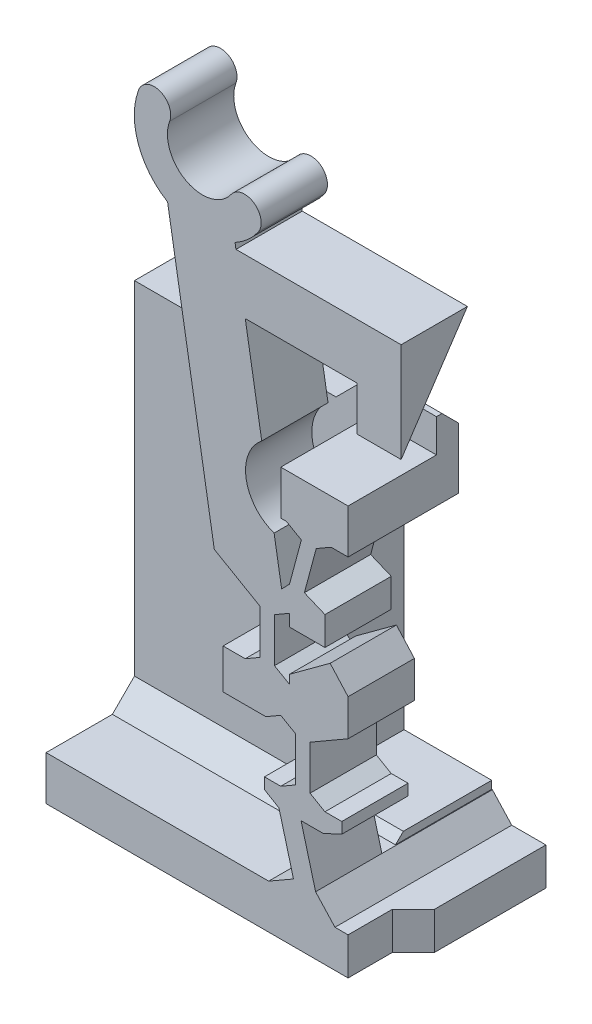
SolidWorks part; units mm, degrees
material "Nylon 6/12"
ref_plane "Front Plane" through (0, 0, 0) normal (0, 0, 1) x (1, 0, 0)
ref_plane "Top Plane" through (0, 0, 0) normal (0, 1, 0) x (1, 0, 0)
ref_plane "Right Plane" through (0, 0, 0) normal (1, 0, 0) x (0, 0, -1)
sketch "Sketch-SkeletonConfigUp" plane through (0, 0, 0) normal (0, 0, 1) x (1, 0, 0)
  line L0 (0, 0) -> (0, -50000) construction
  line L1 (0, 0) -> (4.5811, 6.2164) construction
  line L2 (9.8143, 13.3177) -> (4.5811, 13.945) construction
  line L3 (4.5811, 13.945) -> (2.9713, 10.4094) construction
  line L4 (2.9713, 10.4094) -> (4.5811, 6.2164) construction
  line L5 (4.5811, 13.945) -> (6.2429, 19.1409) construction
  line L6 (2.9713, 10.4094) -> (0.0405, 27.8193) construction
  line L7 (4.5811, 6.2164) -> (9.8143, 13.3177) construction
  line L8 (-587.3593, -797.0242) -> (9.8143, 13.3177) construction
  dimension "D2" = 7.7221
  dimension "D3" = 8.8212
  dimension "D4" = 5.2707
  dimension "D5" = 119.553
  dimension "D6" = 3.8848
  dimension "D7" = 5.4552
  dimension "D8" = 17.6549
  dimension "D9" = 4.4914
  dimension "D10" = 6.745
  dimension "D11" = 145.964
  dimension "D12" = 143.612
sketch "Sketch-SkeletonConfigDown" plane through (0, 0, 0) normal (0, 0, 1) x (1, 0, 0)
  line L0 (0, 0) -> (0, -50000) construction
  line L1 (0, 0) -> (4.5811, 6.2164) construction
  line L2 (9.8143, 13.3177) -> (4.5811, 13.945) construction
  line L3 (4.5811, 13.945) -> (6.1909, 10.4094) construction
  line L4 (6.1909, 10.4094) -> (4.5811, 6.2164) construction
  line L5 (4.5811, 13.945) -> (1.753, 18.6098) construction
  line L6 (6.1909, 10.4094) -> (-8.8652, 19.6294) construction
  line L7 (4.5811, 6.2164) -> (9.8143, 13.3177) construction
  line L8 (-589.9357, -800.5203) -> (9.8143, 13.3177) construction
  dimension "D2" = 7.7221
  dimension "D3" = 8.8212
  dimension "D4" = 5.2707
  dimension "D5" = 119.553
  dimension "D6" = 3.8848
  dimension "D7" = 5.4552
  dimension "D8" = 17.6549
  dimension "D9" = 4.4914
  dimension "D10" = 6.745
  dimension "D11" = 145.964
  dimension "D1" = 143.612
ref_plane "Plane-Cam Base" through (9.128, 0, 0) normal (1, 0, 0) x (0, 0, -1)
ref_plane "Plane-Down-to-Up Derailleur Clearance" through (6.628, 0, 0) normal (1, 0, 0) x (0, 0, -1)
ref_plane "Plane-Cam Cavity Roof" through (5.128, 0, 0) normal (1, 0, 0) x (0, 0, -1)
sketch "Sketch-SwitchBossUp" plane through (0, 0, 0) normal (0, 0, 1) x (1, 0, 0)
  line L0 (3.5811, 11.4759) -> (3.5811, 12.945) construction
  line L5 (5.5811, 12.5552) -> (5.5811, 11.263)
  line L7 (1.5115, 25.1048) -> (1.5536, 24.8548)
  line L8 (-0.4607, 24.7728) -> (1.6966, 11.9577) construction
  line L9 (2.9713, 10.4094) -> (0.0405, 27.8193) construction
  line L11 (0.1364, 21.2256) -> (2.1086, 21.5576) construction
  line L15 (6.628, -23.7286) -> (6.628, 23.7286) construction
  line L16 (2.9713, 10.4094) -> (4.5811, 6.2164) construction
  line L17 (3.5811, 12.945) -> (3.5811, 14.945) construction
  line L18 (5.5811, 12.945) -> (5.5811, 14.945) construction
  line L19 (4.2561, 13.945) -> (4.9061, 13.945) construction
  line L20 (3.5811, 14.945) -> (5.5811, 14.945) construction
  line L21 (3.5811, 12.945) -> (5.5811, 12.945) construction
  line L22 (4.5811, 12.945) -> (4.5811, 14.945) construction
  line L23 (4.5811, 6.2164) -> (8.5405, 7.1023) construction
  line L24 (1.9713, 9.4094) -> (1.9713, 11.4094) construction
  line L25 (3.9713, 9.4094) -> (3.9713, 11.4094) construction
  line L26 (3.9713, 9.4094) -> (1.9713, 9.4094) construction
  line L27 (1.9713, 11.4094) -> (3.9713, 11.4094) construction
  line L28 (3.5811, 7.2164) -> (5.5811, 7.2164) construction
  line L29 (3.5811, 7.2164) -> (3.5811, 5.2164) construction
  line L30 (5.5811, 7.2164) -> (5.5811, 5.2164) construction
  line L31 (3.5811, 5.2164) -> (5.5811, 5.2164) construction
  line L32 (4.9061, 6.2164) -> (4.2561, 6.2164) construction
  line L40 (3.2963, 10.4094) -> (2.6463, 10.4094) construction
  line L66 (0.0405, 27.8193) -> (0.0405, 50027.8193) construction
  line L75 (3.9992, 3.937) -> (4.6576, 1.4797) construction
  line L76 (5.5811, 11.263) -> (5.5811, 12.5552) construction
  line L77 (5.5811, 7.6061) -> (6.628, 8.2105)
  line L80 (5.8152, 10.763) -> (6.628, 9.8603)
  line L81 (9.128, 1033.2419) -> (9.128, 20.0586) construction
  line L85 (6.9307, 9.5241) -> (8.5405, 7.7363) construction
  line L88 (5.7256, 17.3347) -> (6.628, 17.3347)
  line L92 (3.7762, 8.3129) -> (6.9307, 9.5241) construction
  line L98 (1.9713, 9.0197) -> (0.9713, 9.0197)
  line L99 (0.9713, 9.0197) -> (0.9713, 7.2164)
  line L100 (0.9713, 7.2164) -> (2.9061, 7.2164)
  line L101 (4.5811, 6.2164) -> (6.9307, 9.5241) construction
  line L103 (0.0405, 27.8193) -> (1.9448, 26.4638) construction
  line L104 (6.9307, 9.5241) -> (8.5405, 7.7363) construction
  line L107 (1.9713, 9.4094) -> (1.9713, 9.0197) construction
  line L109 (0.0405, 27.8193) -> (-2.1498, 28.6358) construction
  line L111 (6.628, 9.8603) -> (6.628, 8.2105)
  line L112 (6.628, 9.8603) -> (6.9307, 9.5241) construction
  line L113 (2.8424, 4.8267) -> (2.8424, 4.3267)
  line L114 (7.3693, 7.7363) -> (7.3563, 7.7363) construction
  line L121 (5.1576, -1.1226) -> (5.1576, 1.4797) construction
  line L122 (9.028, 22.3548) -> (9.028, 20.3548)
  line L127 (5.5811, 15.3347) -> (5.5811, 14.945) construction
  line L130 (6.0345, 0.5265) -> (6.628, 0.5265)
  line L132 (2.8424, 4.3267) -> (3.4992, 3.937)
  line L133 (2.9713, 10.4094) -> (6.1909, 10.4094) construction
  line L134 (4.5811, 10.4094) -> (4.5811, 13.945) construction
  line L135 (4.5811, 10.4094) -> (4.5811, 6.2164) construction
  line L137 (3.9713, 9.4094) -> (5.5811, 7.2164) construction
  line L139 (5.8152, 10.763) -> (3.9713, 9.4094)
  line L141 (4.1576, 1.4797) -> (3.0345, 0.8347)
  line L142 (3.0345, 0.8347) -> (3.0345, -1.1653)
  line L143 (9.128, 20.0586) -> (9.128, 18.3333) construction
  line L145 (9.128, 16.6071) -> (9.128, -49992.4167) construction
  line L147 (5.5811, 11.263) -> (5.5811, 12.5552) construction
  line L150 (3.0345, -1.1653) -> (6.628, -1.1653)
  line L151 (3.4992, 3.937) -> (4.4992, 3.937) construction
  line L152 (4.5126, 14.945) -> (3.9767, 12.945)
  line L153 (5.1855, 14.945) -> (4.6496, 12.945)
  line L157 (3.5811, 17.3347) -> (3.5811, 15.3347)
  line L158 (5.8605, 15.3347) -> (6.628, 15.3347)
  line L162 (3.2963, 11.4094) -> (3.2963, 9.4094)
  line L164 (2.6463, 11.4094) -> (2.6463, 9.4094)
  line L169 (4.2561, 7.2164) -> (4.2561, 5.2164)
  line L170 (4.9061, 5.2164) -> (4.9061, 7.2164)
  line L175 (4.2561, 7.2164) -> (3.5811, 7.6061)
  line L176 (4.9061, 7.2164) -> (5.5811, 7.6061)
  line L177 (5.5811, 7.2164) -> (5.5811, 7.6061) construction
  line L179 (4.2561, 5.2164) -> (3.5811, 4.8267)
  line L180 (3.5811, 5.2164) -> (3.5811, 4.8267) construction
  line L181 (3.5811, 4.8267) -> (2.8424, 4.8267)
  line L183 (4.9061, 5.2164) -> (5.5811, 4.8267)
  line L184 (5.5811, 5.2164) -> (5.5811, 4.8267) construction
  line L186 (9.128, -23.7286) -> (9.128, 23.7286) construction
  line L187 (2.6463, 9.4094) -> (1.9713, 9.0197)
  line L188 (3.2963, 9.4094) -> (3.9713, 9.0197)
  line L189 (3.2963, 11.4094) -> (3.9713, 11.7991)
  line L190 (2.6463, 11.4094) -> (1.6966, 11.9577)
  line L191 (3.9713, 11.4094) -> (3.9713, 11.7991) construction
  line L192 (3.9713, 11.7991) -> (3.9713, 11.263)
  line L193 (4.6496, 12.945) -> (5.5811, 12.5552)
  line L194 (3.9767, 12.945) -> (3.6203, 12.5779)
  line L195 (3.9713, 11.263) -> (5.5811, 11.263)
  line L196 (3.9713, 9.4094) -> (3.9713, 9.0197)
  line L197 (3.5811, 7.2164) -> (3.5811, 7.6061) construction
  line L199 (3.5811, 7.6061) -> (2.9061, 7.2164)
  line L201 (2.8424, 4.3267) -> (2.8424, 3.937) construction
  line L202 (2.8424, 3.937) -> (3.4992, 3.937) construction
  line L205 (3.0345, 1.4797) -> (3.0345, 0.8347) construction
  line L206 (5.1576, 1.4797) -> (6.0345, 0.5265)
  line L207 (9.128, 18.3333) -> (9.128, 16.6071) construction
  line L208 (6.628, -1.1653) -> (6.628, 0.5265)
  line L209 (9.128, 20.0586) -> (9.128, 16.6071) construction
  line L211 (5.1576, 1.4797) -> (4.4992, 3.937)
  line L212 (4.1576, 1.4797) -> (3.4992, 3.937)
  line L214 (4.5126, 14.945) -> (3.8375, 15.3347)
  line L215 (3.8375, 15.3347) -> (3.5811, 15.3347)
  line L216 (5.1855, 14.945) -> (5.8605, 15.3347)
  line L217 (5.5811, 12.945) -> (5.5811, 12.5552) construction
  line L218 (5.1855, 14.945) -> (5.1855, 15.3347) construction
  line L219 (5.8605, 15.3347) -> (3.8375, 15.3347) construction
  line L221 (9.028, 22.3548) -> (9.028, 24.8548)
  line L224 (3.5811, 17.3347) -> (5.7256, 17.3347)
  line L232 (6.628, 15.3347) -> (6.628, 17.3347)
  line L236 (1.5536, 24.8548) -> (9.028, 24.8548)
  line L240 (4.4992, 3.937) -> (5.4992, 3.937)
  line L241 (5.4992, 3.937) -> (6.3424, 4.3267)
  line L248 (7.028, 22.3548) -> (1.9744, 22.3548)
  line L249 (1.9744, 22.3548) -> (2.7198, 17.9273)
  line L250 (9.028, 20.3548) -> (7.028, 20.3548)
  line L251 (7.028, 20.3548) -> (7.028, 22.3548)
  line L252 (3.2801, 14.5986) -> (3.6203, 12.5779)
  line L253 (4.2672, 14.0291) -> (4.895, 13.8608) construction
  line L254 (5.1576, 1.4797) -> (4.1576, 1.4797) construction
  line L255 (4.1576, 1.4797) -> (3.0345, 1.4797) construction
  line L256 (1.6966, 11.9577) -> (0.5733, 12.6062)
  line L257 (0.5733, 12.6062) -> (-1.5413, 25.1678)
  line L367 (5.5811, 4.8267) -> (6.3424, 4.8267)
  line L368 (6.3424, 4.8267) -> (6.3424, 4.3267)
  arc A0 (1.5115, 25.1048) -> (2.5558, 26.0289) centre (0.0405, 27.8193) ccw
  arc A1 (-1.5413, 25.1678) -> (-2.8525, 28.8978) centre (0.0405, 27.8193) cw
  arc A2 (-2.8525, 28.8978) -> (-1.447, 28.3738) centre (-2.1498, 28.6358) cw
  arc A3 (2.5558, 26.0289) -> (1.3338, 26.8987) centre (1.9448, 26.4638) ccw
  arc A4 (-1.447, 28.3738) -> (1.3338, 26.8987) centre (0.0405, 27.8193) ccw
  arc A5 (3.5811, 12.945) -> (3.5811, 14.945) centre (3.1778, 13.945) ccw construction
  arc A6 (5.5811, 12.945) -> (5.5811, 14.945) centre (5.9843, 13.945) cw construction
  arc A7 (2.5293, 9.921) -> (1.9713, 11.4094) centre (1.568, 10.4094) ccw construction
  arc A8 (3.9713, 11.4094) -> (3.9713, 9.4094) centre (4.3745, 10.4094) ccw construction
  arc A9 (3.5811, 7.2164) -> (3.5811, 5.2164) centre (3.1779, 6.2164) cw construction
  arc A10 (5.5811, 7.2164) -> (5.5811, 5.2164) centre (5.9844, 6.2164) ccw construction
  circle A28 centre (0.0405, 27.8193) radius 2.3375 construction
  arc A29 (1.9713, 9.4094) -> (2.5293, 9.921) centre (1.568, 10.4094) ccw construction
  arc A30 (3.2801, 14.5986) -> (2.7198, 17.9273) centre (3.9114, 16.4164) cw
  arc A31 (-0.4607, 24.7728) -> (-1.5413, 25.1678) centre (0.0405, 27.8193) cw construction
  point P53 (4.5811, 13.945)
  point P63 (2.9713, 10.4094)
  point P93 (1.1225, 21.3916)
  dimension "D23" = 1.5875
  dimension "D24" = 0.75
  dimension "D2" = 2
  dimension "D5" = 2
  dimension "D8" = 42
  dimension "D16" = 42
  dimension "D27" = 120
  dimension "D28" = 120
  dimension "D29" = 120
  dimension "D30" = 120
  dimension "D31" = 120
  dimension "D32" = 120
  dimension "D33" = 120
  dimension "D34" = 120
  dimension "D17" = 0.5
  dimension "D21" = 2
  dimension "D38" = 2
  dimension "D39" = 0.5
  dimension "D40" = 60
  dimension "D41" = 1
  dimension "D42" = 45
  dimension "D43" = 120
  dimension "D10" = 15
  dimension "D25" = 15
  dimension "D26" = 120
  dimension "D35" = 120
  dimension "D20" = 3
  dimension "D48" = 2
  dimension "D82" = 1
  dimension "D83" = 3.5
  dimension "D14" = 2.5
  dimension "D15" = 0.25
  dimension "D7" = 2
  dimension "D9" = 2
  dimension "D6" = 0.65
  dimension "D12" = 1
  dimension "D13" = 1
extrude "Boss-Switch Body" add sketch "Sketch-SwitchBossUp" along normal blind 3
sketch "Sketch1" plane through (0, 0, 0) normal (0, 0, -1) x (-1, 0, 0)
  line L1 (-7.5811, -1.1653) -> (0.4122, -1.1653)
  line L2 (-7.5811, -1.1653) -> (-7.5811, 0.5265)
  line L4 (0.4122, -1.1653) -> (0.4122, 0.8347)
  line L5 (-3.5811, 18.8347) -> (-7.5811, 18.8347)
  line L10 (-7.5811, 18.8347) -> (-7.5811, 15.3347)
  line L11 (-4.1576, 1.4797) -> (-5.1576, 1.4797)
  line L12 (-7.5811, 15.3347) -> (-3.5811, 15.3347)
  line L13 (-4.1576, 1.4797) -> (-3.0345, 0.8347)
  line L14 (-3.5811, 15.3347) -> (-3.5811, 18.8347)
  line L20 (-4.4992, 3.937) -> (-5.1576, 1.4797) construction
  line L22 (-3.0345, -1.1653) -> (-6.628, -1.1653) construction
  line L23 (-3.0345, 0.8347) -> (0.4122, 0.8347)
  line L24 (-5.1576, 1.4797) -> (-6.0345, 0.5265)
  line L25 (-6.0345, 0.5265) -> (-7.5811, 0.5265)
  dimension "D1" = 3.5
extrude "Boss-Flange Width" add sketch "Sketch1" along normal blind 5
ref_plane "Plane-Sta2Sit Groove" through (0.0405, 0, 0) normal (1, 0, 0) x (0, 0, -1)
ref_plane "Plane-Cam Outer Surface" through (-12.0395, 0, 0) normal (1, 0, 0) x (0, 0, -1)
ref_plane "Plane-FlangeTop" through (-7.0395, 0, 0) normal (1, 0, 0) x (0, 0, -1)
sketch "Sketch2" plane through (-7.0395, 0, 0) normal (1, 0, 0) x (0, 0, -1)
  line L0 (5, 15.3347) -> (-3, 15.3347) construction
  line L1 (5, 17.3347) -> (1, 17.3347)
  line L2 (5, 17.3347) -> (5, 15.3347)
  line L3 (5, 15.3347) -> (1, 15.3347)
  line L4 (1, 17.3347) -> (1, 15.3347)
  line L5 (-3, -1.1653) -> (-3, 0.5265) construction
  line L11 (5, 0.8347) -> (-3, 0.8347)
  line L12 (5, 0.8347) -> (5, -1.1653)
  line L13 (5, -1.1653) -> (-3, -1.1653)
  line L14 (-3, 0.8347) -> (-3, -1.1653)
  line L15 (0, 10.4094) -> (0, 27.8193) construction
  line L17 (5, 0.5265) -> (5, -1.1653) construction
  line L18 (-3, 0.8347) -> (0, 0.8347) construction
  dimension "D1" = 1
  dimension "D2" = 2
extrude "Boss-Flange Height" add sketch "Sketch2" along normal up to surface (11.6675 mm away)
sketch "Sketch10" plane through (0, 15.3347, 0) normal (0, 1, 0) x (1, 0, 0)
  line L0 (9.128, -23.7286) -> (9.128, 23.7286) construction
  line L1 (7.5811, 5) -> (5.128, 5)
  line L2 (7.5811, 5) -> (7.5811, 2)
  line L3 (7.5811, 2) -> (5.128, 2)
  line L5 (4.628, 7) -> (4.628, 1) construction
  line L6 (3.5811, 1) -> (-7.0395, 1) construction
  line L8 (5.128, 5) -> (5.128, 2)
  dimension "D1" = 1
  dimension "D2" = 0.5
  dimension "D3" = 4.5
extrude "Cut-Up-To-Down Derailleur Clearance" cut sketch "Sketch10" along normal up to next
sketch "Sketch17" plane through (0, 15.3347, 0) normal (0, -1, 0) x (1, 0, 0)
  line L0 (5.128, -5) -> (-7.0395, -5)
  line L1 (5.128, -5) -> (-7.0395, -5) construction
  line L2 (-7.0395, -5) -> (-7.0395, -1)
  line L3 (-7.0395, -1) -> (5.128, -1)
  line L4 (5.128, -1) -> (5.128, -5)
  line L5 (-7.0395, -1) -> (-7.0395, -5) construction
extrude "Boss-Flange Support" add sketch "Sketch17" along normal up to surface (14.5 mm away) up to face at (-2.0025, 0.8347, -1)
sketch "Sketch-HolePositions" plane through (0, -1.1653, 0) normal (0, -1, 0) x (1, 0, 0)
  line L0 (-7.0395, -3) -> (7.5811, -3) construction
  line L1 (7.5811, -5) -> (-7.0395, -5) construction
  line L2 (7.5811, -5) -> (7.5811, 0) construction
  line L4 (-7.0395, -22.2167) -> (-7.0395, 22.2167) construction
  point P6 (-5.0395, -3)
  point P7 (-0.5395, -3)
  dimension "D1" = 2
  dimension "D2" = 4.5
  dimension "D3" = 2
sketch "Sketch6" plane through (0, -1.1653, 0) normal (0, -1, 0) x (-1, 0, 0)
  point P0 (5.0395, 3)
  point P3 (0.5395, 3)
hole_wizard "Tap Drill for M2x0.4 Tap1" positions "Sketch6" profile "Sketch5" hole size "M2x0.4" standard "ANSI Metric" end condition through all
sketch "Sketch5" plane through (-5.0395, -1.1653, -3) normal (1, 0, 0) x (0, 0, -1)
  line L0 (0, 0) -> (0, 30.5511)
  line L1 (0, 30.5511) -> (0.8, 30.5511)
  line L2 (0.8, 30.5511) -> (0.8, 0)
  line L5 (0.8, 0) -> (0, 0)
  line L11 (0, -6.35) -> (0, 107.95) construction
  dimension "Thru Hole Dia." = 1.6
  dimension "Thru Hole Depth" = 30.5511
sketch "Sketch9" plane through (0, -1.1653, 0) normal (0, -1, 0) x (1, 0, 0)
  point P0 (-5.0395, -3)
  point P3 (-0.5395, -3)
hole_wizard "M2 Clearance Hole2" positions "Sketch9" profile "Sketch8" hole size "M2" standard "ANSI Metric"
sketch "Sketch8" plane through (-5.0395, -1.1653, -3) normal (1, 0, 0) x (0, 0, -1)
  line L0 (0, 0) -> (0, 15.721)
  line L1 (0, 15.721) -> (1.2, 15)
  line L2 (1.2, 15) -> (1.2, 0)
  line L5 (1.2, 0) -> (0, 0)
  line L10 (0, 15.721) -> (-1.2, 15) construction
  line L11 (0, -6.35) -> (0, 107.95) construction
  dimension "Hole Dia." = 2.4
  dimension "Hole Depth" = 15
  dimension "Drill Angle" = 118
sketch "Sketch-Measurements for Derailleur Ramps" [suppressed] plane through (0, 0, 0) normal (0, 0, 1) x (1, 0, 0)
  line L0 (3.184, 15.1695) -> (2.4687, 19.4188)
  line L1 (2.8264, 17.2941) -> (1.8402, 17.1281)
  line L2 (2.9713, 10.4094) -> (0.0405, 27.8193) construction
  line L3 (1.8402, 17.1281) -> (-1.3081, 15.0016)
  line L4 (6.1909, 10.4094) -> (-8.8652, 19.6294) construction
  line L5 (1.8402, 17.1281) -> (2.6012, 12.6077)
  line L6 (2.6012, 12.6077) -> (-1.3081, 15.0016)
  line L7 (0.2661, 16.0649) -> (0.2661, 17.1281)
  line L8 (0.2661, 17.1281) -> (1.8402, 17.1281)
  line L9 (6.1909, 10.4094) -> (2.9713, 10.4094)
  line L10 (5.386, 8.3129) -> (3.7762, 8.3129)
  line L11 (2.6116, 18.5698) -> (1.5115, 25.1048) construction
  line L12 (6.1909, 10.4094) -> (4.5811, 6.2164) construction
  line L13 (4.5811, 8.3129) -> (4.5811, 8.7912)
  line L14 (4.5811, 6.2164) -> (5.386, 8.3129)
  line L15 (2.9713, 10.4094) -> (4.5811, 6.2164) construction
  line L16 (3.7762, 8.3129) -> (4.5811, 6.2164)
  line L17 (5.386, 8.3129) -> (5.386, 8.7912)
  dimension "D1" = 1.5742
  dimension "D2" = 0.8049
ref_plane "Plane1" through (0, 7.1023, 0) normal (0, 1, 0) x (1, 0, 0)
ref_plane "Plane-Cantilever Cut" [suppressed] through (7.0848, 8.5204, -1.9058) normal (-0.6301, -0.7578, 0.1695) x (-0.7765, 0.6151, -0.1368)
sketch "Sketch14" [suppressed] plane through (7.0848, 8.5204, -1.9058) normal (-0.6301, -0.7578, 0.1695) x (-0.7765, 0.6151, -0.1368)
  line L0 (2.3023, -1.6911) -> (-0.3551, -1.6911)
  line L2 (2.3023, -4.3362) -> (2.3023, -1.6911)
  line L3 (-0.3551, -1.6911) -> (-0.3551, -4.4608)
  line L5 (-0.3551, -4.4608) -> (1.0087, -5.0843)
  line L6 (1.0087, -5.0843) -> (2.3023, -4.3362)
extrude "Cut-Down-to-Up Cantilever Slope" [suppressed] cut sketch "Sketch14" against normal up to next
ref_plane "Plane-Symmetry Plane" through (0, 0, 1.5) normal (0, 0, 1) x (1, 0, 0)
sketch "Sketch-Cable Center Point" plane through (0, 0, 1.5) normal (0, 0, 1) x (1, 0, 0)
  line L0 (0.0405, 27.8193) -> (0.1722, 27.0366)
  line L1 (2.9713, 10.4094) -> (0.0405, 27.8193) construction
  point P0 (0.0405, 27.8193)
  dimension "D1" = 0.7937
chamfer "Chamfer-Flange Support" distance 1.5 angle 45 1 edges at (3.5811, 17.3347, -3)
chamfer "Chamfer-Flange Support 2" distance 1.5 angle 45 2 edges at (5.128, 17.0847, -2) (5.128, 15.3347, -1.5)
chamfer "Chamfer-Flange Support 3" distance 1 angle 45 1 edges at (-2.0025, 0.8347, -1)
chamfer "Chamfer7" [suppressed] distance 1 angle 45
sketch "Sketch23" plane through (0, 0, -1) normal (0, 0, 1) x (1, 0, 0)
  line L0 (5.128, 1.8347) -> (1.1605, 1.8347)
  line L1 (-7.0395, 1.8347) -> (5.128, 1.8347) construction
  line L2 (1.1605, 1.8347) -> (1.1605, 13.8347)
  line L3 (1.1605, 13.8347) -> (5.128, 13.8347)
  line L4 (5.128, 13.8347) -> (5.128, 1.8347)
  line L5 (0.6605, -1.1653) -> (0.6605, 13.8347) construction
  dimension "D1" = 0.5
extrude "Cut-Gap for Printing" cut sketch "Sketch23" against normal through all
sketch "Sketch25" plane through (0, 0, 0) normal (0, 0, 1) x (1, 0, 0)
  line L0 (6.628, 15.3347) -> (7.5811, 15.3347)
  line L1 (7.5811, 15.3347) -> (7.5811, 18.8347)
  line L2 (7.5811, 18.8347) -> (6.628, 18.8347)
  line L3 (6.628, -23.7286) -> (6.628, 23.7286) construction
  line L4 (7.5811, 18.8347) -> (3.5811, 18.8347) construction
  line L5 (6.628, 18.8347) -> (6.628, 15.3347)
  line L6 (7.5811, 18.8347) -> (7.5811, 15.3347) construction
extrude "Cut-Derailleur Clearance" cut sketch "Sketch25" against normal through all
chamfer "Chamfer8" distance 1 angle 45 1 edges at (6.628, -0.3194, 0)
ref_plane "Plane2" through (-3.0866, 5.589, 8.3835) normal (0.2929, -0.5304, -0.7956) x (-0.9561, -0.1625, -0.2437)
sketch "Sketch26" plane through (-3.0866, 5.589, 8.3835) normal (0.2929, -0.5304, -0.7956) x (-0.9561, -0.1625, -0.2437)
  line L0 (-7.553, 20.6804) -> (-7.553, 14.9094)
  line L1 (-12.6703, 20.6804) -> (-5.5238, 20.6804) construction
  line L3 (-7.553, 14.9094) -> (-20.0302, 14.9094)
  line L4 (-20.0302, 14.9094) -> (-20.0302, 20.6804)
  line L5 (-20.0302, 20.6804) -> (-7.553, 20.6804)
extrude "Cut-Up-to-Down Cantilever Slope" cut sketch "Sketch26" along normal up to next
sketch "Sketch27" plane through (5.128, 0, 0) normal (1, 0, 0) x (0, 0, -1)
  line L0 (3.5, 18.8347) -> (3.5, 13.8347) construction
  line L1 (2.5, 18.8347) -> (5, 18.8347)
  line L2 (2.5, 18.8347) -> (2.5, 13.8347)
  line L3 (2.5, 13.8347) -> (5, 13.8347)
  line L4 (5, 18.8347) -> (5, 13.8347)
  dimension "D1" = 1
extrude "Cut-Wide Derailleur Clearance" cut sketch "Sketch27" against normal blind 4 and the other way through all
chamfer "Chamfer9" distance 1.25 angle 45 1 edges at (4.8545, 18.8347, -2.5)
sketch "Sketch28" plane through (0, 0, -1) normal (0, 0, 1) x (1, 0, 0)
  line L0 (3.5811, 18.8347) -> (6.628, 18.8347)
  line L1 (6.628, 18.8347) -> (6.628, 17.3347)
  line L2 (6.628, 17.3347) -> (3.5811, 17.3347)
  line L3 (3.5811, 17.3347) -> (3.5811, 18.8347)
extrude "Cut-Extrude1" cut sketch "Sketch28" along normal up to surface (1 mm away) up to face at (5.1045, 18.0847, 0)
equation "\"axle-diameter\"=2"
equation "\"switch-thickness\"=12"
equation "\"base-width\"=4.0"
equation "\"axle-bushing-radius\"=3"
equation "\"clearance\"= 0.25"
equation "\"arm-width\"=1.5"
equation "\"min-diameter\"=70"
equation "\"alpha\"=143.6120"
equation "\"gamma\"=119.5526"
equation "\"delta\"=145.9637"
equation "\"epsilon\"=6.7452"
equation "\"l_AB\"=8.8212"
equation "\"l_AC\"=4.4914"
equation "\"l_BD\"=5.2707"
equation "\"l_CD\"=3.8848"
equation "\"l_CE\"=17.6549"
equation "\"l_DF\"=5.4552"
equation "\"l_OA\"=7.7221"
equation "\"D2@Sketch-SkeletonConfigUp\" = \"l_OA\""
equation "\"D3@Sketch-SkeletonConfigUp\" = \"l_AB\""
equation "\"D4@Sketch-SkeletonConfigUp\" = \"l_BD\""
equation "\"D5@Sketch-SkeletonConfigUp\" = \"gamma\""
equation "\"D6@Sketch-SkeletonConfigUp\" = \"l_CD\""
equation "\"D7@Sketch-SkeletonConfigUp\" = \"l_DF\""
equation "\"D8@Sketch-SkeletonConfigUp\" = \"l_CE\""
equation "\"D9@Sketch-SkeletonConfigUp\" = \"l_AC\""
equation "\"D_groove\"=3.175"
equation "\"D7@Sketch-SkeletonConfigDown\" = \"l_DF\""
equation "\"D6@Sketch-SkeletonConfigDown\" = \"l_CD\""
equation "\"D2@Sketch-SkeletonConfigDown\" = \"l_OA\""
equation "\"D3@Sketch-SkeletonConfigDown\" = \"l_AB\""
equation "\"D9@Sketch-SkeletonConfigDown\" = \"l_AC\""
equation "\"D8@Sketch-SkeletonConfigDown\" = \"l_CE\""
equation "\"D5@Sketch-SkeletonConfigDown\" = \"gamma\""
equation "\"D4@Sketch-SkeletonConfigDown\" = \"l_BD\""
equation "\"D1@Sketch-SkeletonConfigDown\" = \"alpha\""
equation "\"hinge_length\"=1.5"
equation "\"hinge_depth\"=0.25"
equation "\"D10@Sketch-SkeletonConfigUp\"=\"epsilon\""
equation "\"D11@Sketch-SkeletonConfigUp\"=\"delta\""
equation "\"D12@Sketch-SkeletonConfigUp\"=\"alpha\""
equation "\"D11@Sketch-SkeletonConfigDown\"=\"delta\""
equation "\"D10@Sketch-SkeletonConfigDown\"=\"epsilon\""
equation "\"EE_dx\"=8.9056"
equation "\"EE_dy\"=8.1898"
equation "\"r_groove\"=\"D_groove\"/2"
equation "\"t_wall\"=25.4/16"
equation "\"width_lower\"=\"D_groove\"+\"t_wall\""
equation "\"cable_to_bottom\"=30.6257"
equation "\"switch_EE-up_base_dy\"=24"
equation "\"switch_EE-down_base_dy\"=16"
equation "\"D_axle\"=25.4/8"
equation "\"D_up_to_down\"=16"
equation "\"D_down_to_up\"=25"
equation "\"t_cam_base\"=7.5"
equation "\"D23@Sketch-SwitchBossUp\"=\"D_groove\"/2"
equation "\"D1@Sketch-Cable Center Point\"=\"D_groove\"/4"
